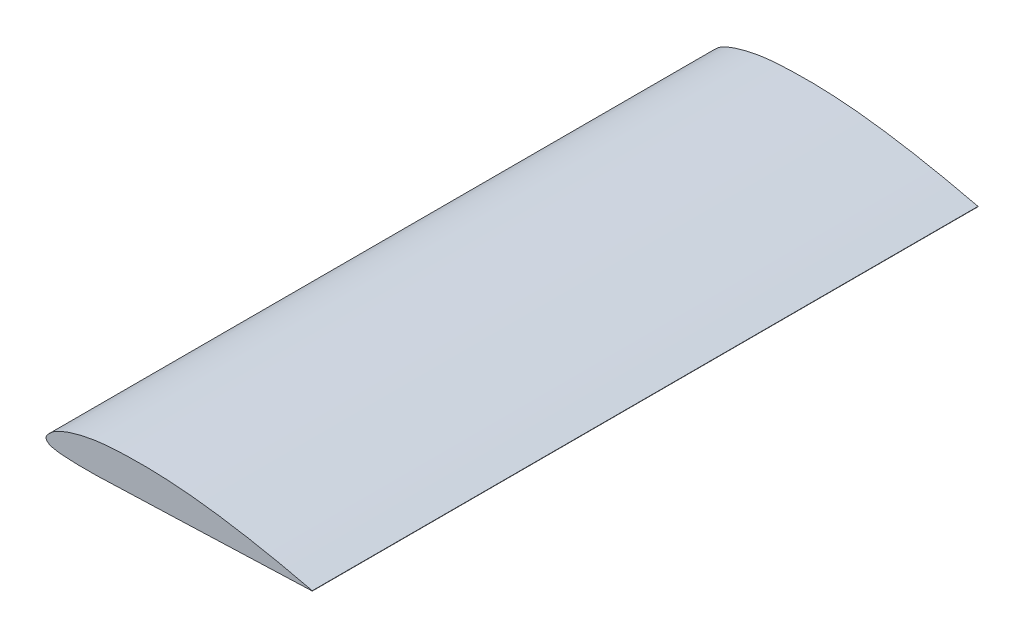
SolidWorks part; units mm, degrees
ref_plane "Front Plane" through (0, 0, 0) normal (0, 0, 1) x (1, 0, 0)
ref_plane "Top Plane" through (0, 0, 0) normal (0, 1, 0) x (1, 0, 0)
ref_plane "Right Plane" through (0, 0, 0) normal (1, 0, 0) x (0, 0, -1)
curve "Curve1"
  spline degree 3 poles (25.4, 0.0152, 0) (25.3153, 0.0353, 0) (25.146, 0.0754, 0) (24.892, 0.1355, 0) (24.6381, 0.1953, 0) (24.2995, 0.2744, 0) (23.8763, 0.3719, 0) (23.3683, 0.4859, 0) (22.8603, 0.5973, 0) (22.3523, 0.7062, 0) (21.8443, 0.8125, 0) (21.3363, 0.9162, 0) (20.8283, 1.017, 0) (20.3203, 1.1151, 0) (19.8123, 1.2102, 0) (19.3043, 1.3024, 0) (18.7962, 1.3915, 0) (18.2882, 1.4777, 0) (17.7802, 1.5609, 0) (17.2722, 1.6409, 0) (16.7643, 1.7177, 0) (16.2563, 1.7908, 0) (15.7483, 1.8601, 0) (15.2403, 1.9251, 0) (14.7323, 1.9856, 0) (14.2242, 2.0416, 0) (13.7162, 2.093, 0) (13.2082, 2.1398, 0) (12.7002, 2.182, 0) (12.1922, 2.2197, 0) (11.6842, 2.2524, 0) (11.1761, 2.2798, 0) (10.6681, 2.3014, 0) (10.1601, 2.3168, 0) (9.652, 2.3257, 0) (9.144, 2.3283, 0) (8.636, 2.3252, 0) (8.128, 2.3169, 0) (7.6199, 2.3039, 0) (7.1119, 2.2871, 0) (6.6038, 2.2641, 0) (6.0956, 2.2327, 0) (5.5873, 2.1902, 0) (5.079, 2.1342, 0) (4.5707, 2.0617, 0) (4.0625, 1.9727, 0) (3.5542, 1.8677, 0) (3.0455, 1.7457, 0) (2.5366, 1.6033, 0) (2.0278, 1.436, 0) (1.6043, 1.2762, 0) (1.2667, 1.1258, 0) (1.0109, 0.9949, 0) (0.7528, 0.8393, 0) (0.5145, 0.6577, 0) (0.3356, 0.4854, 0) (0.199, 0.3469, 0) (0.1123, 0.2457, 0) (0.0552, 0.1586, 0) (0.0273, 0.1015, 0) (0.0095, 0.0523, 0) (-0.0066, -0.0188, 0) (0.0016, -0.0927, 0) (0.0273, -0.1571, 0) (0.0549, -0.2082, 0) (0.1111, -0.2828, 0) (0.1967, -0.3619, 0) (0.3302, -0.4523, 0) (0.5196, -0.5255, 0) (0.7613, -0.5742, 0) (1.0151, -0.6246, 0) (1.2693, -0.6634, 0) (1.608, -0.6993, 0) (2.0318, -0.7237, 0) (2.5398, -0.7478, 0) (3.0479, -0.7623, 0) (3.556, -0.7692, 0) (4.064, -0.7694, 0) (4.572, -0.764, 0) (5.08, -0.7541, 0) (5.588, -0.7407, 0) (6.096, -0.7247, 0) (6.604, -0.7067, 0) (7.112, -0.6877, 0) (7.62, -0.6682, 0) (8.128, -0.6491, 0) (8.636, -0.6304, 0) (9.144, -0.6118, 0) (9.652, -0.5934, 0) (10.16, -0.5749, 0) (10.668, -0.5564, 0) (11.176, -0.5378, 0) (11.684, -0.519, 0) (12.192, -0.5004, 0) (12.7, -0.4816, 0) (13.208, -0.4629, 0) (13.716, -0.4443, 0) (14.224, -0.4256, 0) (14.732, -0.407, 0) (15.24, -0.3883, 0) (15.748, -0.3697, 0) (16.256, -0.3511, 0) (16.764, -0.3324, 0) (17.272, -0.3137, 0) (17.78, -0.2951, 0) (18.288, -0.2764, 0) (18.796, -0.2578, 0) (19.304, -0.2391, 0) (19.812, -0.2205, 0) (20.32, -0.2018, 0) (20.828, -0.1831, 0) (21.336, -0.1645, 0) (21.844, -0.1458, 0) (22.352, -0.1271, 0) (22.86, -0.1085, 0) (23.368, -0.0898, 0) (23.876, -0.0712, 0) (24.2993, -0.0556, 0) (24.638, -0.0432, 0) (24.892, -0.0339, 0) (25.146, -0.0246, 0) (25.3153, -0.0183, 0) (25.4, -0.0152, 0) knots 0 0 0 0 0.005028 0.010055 0.015081 0.020105 0.030145 0.040174 0.050191 0.060198 0.070194 0.08018 0.090156 0.100121 0.110076 0.12002 0.129954 0.139879 0.149793 0.159699 0.169594 0.17948 0.189355 0.199219 0.209073 0.218917 0.228751 0.238577 0.248396 0.258207 0.268012 0.277811 0.287604 0.297393 0.307179 0.316964 0.326749 0.336535 0.346322 0.356113 0.365908 0.375711 0.385531 0.395376 0.405259 0.415192 0.425184 0.435248 0.445412 0.455711 0.466191 0.471552 0.477055 0.482787 0.488946 0.494316 0.497126 0.500187 0.502001 0.503128 0.50385 0.50502 0.507318 0.507987 0.509024 0.510668 0.513358 0.515716 0.519949 0.524973 0.529954 0.534903 0.539824 0.54963 0.559425 0.569214 0.579 0.588784 0.59857 0.608356 0.618144 0.627933 0.637724 0.647515 0.657307 0.667099 0.67689 0.686681 0.696472 0.706263 0.716054 0.725846 0.735637 0.745428 0.755219 0.765011 0.774802 0.784593 0.794384 0.804176 0.813967 0.823758 0.833549 0.84334 0.853132 0.862923 0.872714 0.882505 0.892297 0.902088 0.911879 0.92167 0.931461 0.941253 0.951044 0.960835 0.970626 0.980418 0.985313 0.990209 0.995104 1 1 1 1
sketch "Sketch1" plane through (0, 0, 0) normal (0, 0, 1) x (1, 0, 0)
  line L0 (101.6, 0.0609) -> (101.6, -0.0609)
  spline S1 degree 3 poles (101.6, 0.0609) (101.2613, 0.1412) (100.5841, 0.3017) (99.5681, 0.542) (98.5522, 0.7813) (97.198, 1.0977) (95.5052, 1.4875) (93.4731, 1.9437) (91.441, 2.3892) (89.4091, 2.8249) (87.3771, 3.2501) (85.3451, 3.6648) (83.313, 4.068) (81.2811, 4.4604) (79.249, 4.8407) (77.2171, 5.2096) (75.185, 5.5661) (73.153, 5.9109) (71.121, 6.2435) (69.089, 6.5638) (67.0571, 6.871) (65.0251, 7.1634) (62.9931, 7.4404) (60.9611, 7.7004) (58.253, 8.023) (55.5434, 8.3093) (52.8328, 8.5591) (50.8007, 8.7281) (48.7687, 8.8787) (46.0601, 9.0533) (43.3505, 9.185) (40.6403, 9.2674) (38.6081, 9.3027) (36.576, 9.3131) (34.5439, 9.3006) (32.5118, 9.2677) (30.4798, 9.2156) (28.4475, 9.1482) (26.4151, 9.0565) (24.3824, 8.9309) (22.3494, 8.7609) (20.316, 8.5367) (18.2829, 8.2469) (16.2501, 7.8907) (14.2167, 7.4708) (12.1821, 6.9828) (10.1464, 6.413) (8.1111, 5.7439) (6.417, 5.1047) (5.0668, 4.5033) (4.0436, 3.9795) (3.0112, 3.3571) (2.0581, 2.6309) (1.3423, 1.9417) (0.796, 1.3877) (0.449, 0.9827) (0.2208, 0.6342) (0.1092, 0.4059) (0.038, 0.2092) (-0.0266, -0.075) (0.0062, -0.3708) (0.1092, -0.6282) (0.2197, -0.8329) (0.4443, -1.1314) (0.7866, -1.4477) (1.3206, -1.8091) (2.0784, -2.1019) (3.0451, -2.2966) (4.0604, -2.4985) (5.0771, -2.6537) (6.4319, -2.7973) (8.1271, -2.8948) (10.1593, -2.9913) (12.1917, -3.0493) (14.2239, -3.0768) (16.2561, -3.0777) (18.2881, -3.056) (20.9977, -3.0032) (23.707, -2.9226) (26.4161, -2.8268) (28.448, -2.7506) (30.48, -2.6726) (32.512, -2.5962) (34.544, -2.5214) (36.576, -2.4471) (38.608, -2.3735) (40.64, -2.2997) (42.672, -2.2255) (44.704, -2.151) (46.736, -2.0762) (48.768, -2.0015) (50.8, -1.9265) (52.832, -1.8518) (54.864, -1.7771) (58.2507, -1.6528) (61.6373, -1.5285) (65.7013, -1.3794) (68.4107, -1.2797) (71.12, -1.1803) (73.152, -1.1056) (75.184, -1.0311) (77.216, -0.9563) (79.248, -0.8818) (81.28, -0.8071) (83.312, -0.7326) (85.344, -0.6578) (87.376, -0.5833) (89.408, -0.5086) (91.44, -0.4341) (93.472, -0.3593) (95.504, -0.2848) (97.1973, -0.2225) (98.552, -0.1728) (99.568, -0.1355) (100.584, -0.0983) (101.2613, -0.0733) (101.6, -0.0609) knots 0 0 0 0 0.005028 0.010055 0.015081 0.020105 0.030145 0.040174 0.050191 0.060198 0.070194 0.08018 0.090156 0.100121 0.110076 0.12002 0.129954 0.139879 0.149793 0.159699 0.169594 0.17948 0.189355 0.199219 0.209073 0.228751 0.238577 0.248396 0.258207 0.268012 0.287604 0.297393 0.307179 0.316964 0.326749 0.336535 0.346322 0.356113 0.365908 0.375711 0.385531 0.395376 0.405259 0.415192 0.425184 0.435248 0.445412 0.455711 0.466191 0.471552 0.477055 0.482787 0.488946 0.494316 0.497126 0.500187 0.502001 0.503128 0.50385 0.50502 0.507318 0.507987 0.509024 0.510668 0.513358 0.515716 0.519949 0.524973 0.529954 0.534903 0.539824 0.54963 0.559425 0.569214 0.579 0.588784 0.59857 0.608356 0.627933 0.637724 0.647515 0.657307 0.667099 0.67689 0.686681 0.696472 0.706263 0.716054 0.725846 0.735637 0.745428 0.755219 0.765011 0.774802 0.784593 0.813967 0.823758 0.84334 0.853132 0.862923 0.872714 0.882505 0.892297 0.902088 0.911879 0.92167 0.931461 0.941253 0.951044 0.960835 0.970626 0.980418 0.985313 0.990209 0.995104 1 1 1 1
extrude "Boss-Extrude1" add sketch "Sketch1" along normal blind 254
